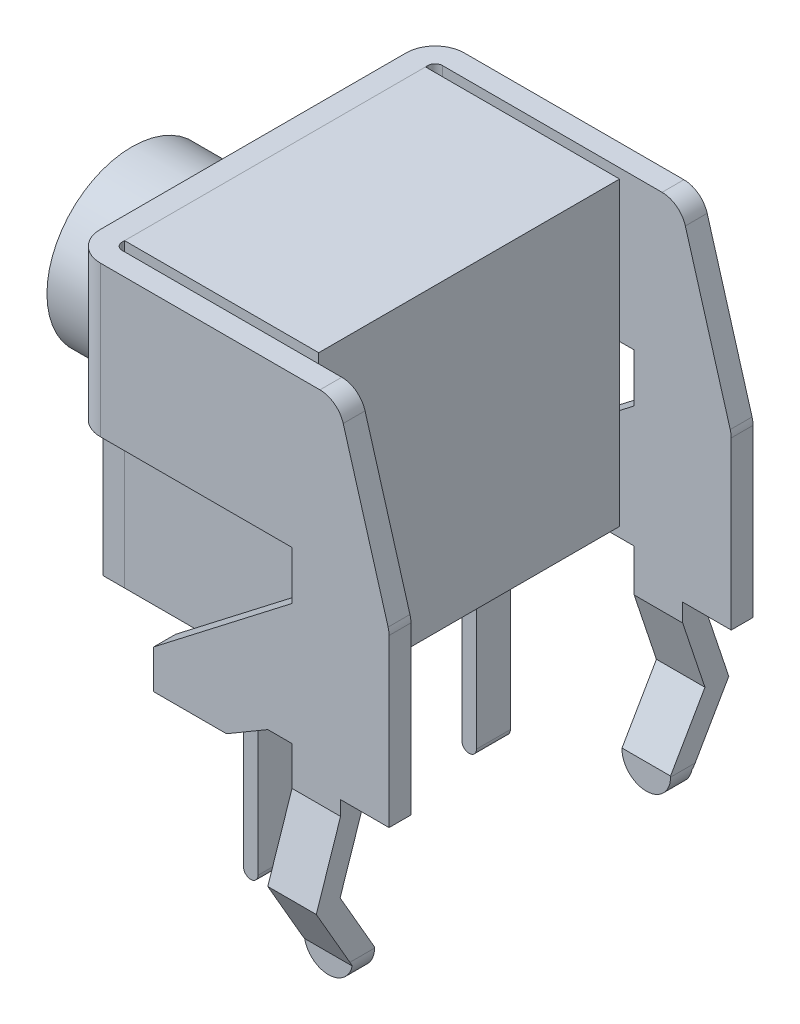
SolidWorks part; units mm, degrees
ref_plane "Front" through (0, 0, 0) normal (0, 0, 1) x (1, 0, 0)
ref_plane "Top" through (0, 0, 0) normal (0, 1, 0) x (1, 0, 0)
ref_plane "Right" through (0, 0, 0) normal (1, 0, 0) x (0, 0, -1)
sketch "草图1" plane through (0, 0, 0) normal (0, 0, 1) x (1, 0, 0)
  line L0 (0, 3.1) -> (0, -3.1)
  line L1 (0, -4) -> (2.4, -4)
  line L2 (6.55, -4) -> (6.55, -0.5)
  line L3 (6.55, -0.5) -> (5.5, 3.1)
  line L4 (5.5, 3.1) -> (0, 3.1)
  line L5 (0, -3.1) -> (0, -4)
  line L6 (2.4, -4) -> (2.4, -7.35) construction
  line L7 (1.0542, -7.5) -> (4.3688, -7.5) construction
  line L8 (2.7, -7.35) -> (2.7, -4) construction
  line L9 (4.55, -4) -> (4.55, -7)
  line L10 (2.7, -4) -> (4.55, -4)
  line L11 (5.55, -7) -> (5.55, -4)
  line L12 (5.55, -4) -> (6.55, -4)
  line L13 (2.4, -4) -> (2.7, -4)
  arc A0 (2.4, -7.35) -> (2.7, -7.35) centre (2.55, -7.35) ccw construction
  arc A1 (4.55, -7) -> (5.55, -7) centre (5.05, -7) ccw
  dimension "D1" = 6.2
  dimension "D2" = 4
  dimension "D3" = 0.3
  dimension "D4" = 1
  dimension "D5" = 2.5
  dimension "D6" = 2.55
  dimension "D7" = 4
  dimension "D8" = 3.5
  dimension "D9" = 5.5
  dimension "D10" = 0.5
extrude "凸台-拉伸1" add sketch "草图1" along normal blind 10 and the other way blind 10
sketch "草图2" plane through (0, 0, 0) normal (1, 0, 0) x (0, 0, -1)
  line L0 (3.75, 3.7782) -> (3.75, -4.3)
  line L1 (3.75, -4.3) -> (4.25, -5.8)
  line L2 (4.25, -5.8) -> (3.5, -7.1)
  line L3 (3.5, -7.1) -> (3.5, -7.9924)
  line L4 (10, 3.1) -> (-10, 3.1) construction
  dimension "D1" = 3.75
  dimension "D2" = 3.5
  dimension "D3" = 0.5
  dimension "D4" = 1.5
  dimension "D5" = 2.8
  dimension "D6" = 7.4
extrude "切除-拉伸1" cut sketch "草图2" against normal through all both and the other way through all
mirror "镜向1" about plane through (0, 0, 0) normal (0, 0, 1) of "切除-拉伸1"
fillet "圆角1" radius 0.6 2 edges at (0, -0.45, -3.75) (0, -0.45, 3.75)
fillet "圆角2" radius 0.5 2 edges at (5.5, 3.1, 0) (6.55, -0.5, 0)
shell "抽壳1" thickness 0.45 removed face at (1.6752, -4, 0) removed face at (4.55, -5.275, 0) removed face at (5.05, -7.1501, 0) removed face at (5.55, -5.275, 0) removed face at (6.05, -4, 0) removed face at (6.55, -2.2857, 0) removed face at (6.5425, -0.5011, 0) removed face at (6.0675, 1.1543, 0) removed face at (5.395, 2.96, 0) removed face at (1.8669, 3.1, 0)
sketch "草图4" plane through (0, 0, 3.75) normal (0, 0, 1) x (1, 0, 0)
  line L0 (-1.45, 0) -> (4.55, 0)
  line L1 (4.55, 0) -> (4.55, -1)
  line L2 (4.55, -1) -> (1.7, -3.2)
  line L3 (1.7, -3.2) -> (1.7, -4)
  line L4 (0.6, -4) -> (4.55, -4) construction
  line L5 (1.7, -4) -> (3.2, -4)
  line L6 (3.2, -4) -> (4.05, -3.5)
  line L7 (4.05, -3.5) -> (4.55, -3.5)
  line L8 (4.55, -3.5) -> (4.55, -9.5)
  line L9 (4.55, -9.5) -> (-1.45, -9.5)
  line L10 (-1.45, -9.5) -> (-1.45, 0)
  line L11 (2.7, -7.35) -> (2.7, -4) construction
  line L12 (2.7, -4) -> (4.55, -4) construction
  dimension "D1" = 0.8
  dimension "D2" = 1
  dimension "D3" = 0.5
  dimension "D4" = 0.5
  dimension "D5" = 0.5
  dimension "D6" = 1.5
  dimension "D7" = 6
  dimension "D8" = 6
extrude "切除-拉伸2" cut sketch "草图4" against normal blind 0.65
mirror "镜向2" about plane through (0, 0, 0) normal (0, 0, 1) of "切除-拉伸2"
sketch "草图5" plane through (0, 0, 0) normal (-1, 0, 0) x (0, 0, 1)
  line L0 (0, -0.5) -> (0, 3.1) construction
  line L1 (-3.1, 3.1) -> (3.1, 3.1) construction
  line L2 (-3.1, 3.1) -> (-3.1, -3.1) construction
  line L3 (-3.1, -3.1) -> (3.1, -3.1) construction
  line L4 (3.1, 3.1) -> (3.1, -3.1) construction
  line L5 (0, -3.1) -> (0, 3.1) construction
  line L6 (-3.1, 0) -> (3.1, 0) construction
  line L7 (-3.15, 3.1) -> (3.15, 3.1) construction
  line L8 (0, 0) -> (-2.1213, 2.1213) construction
  line L9 (-5, -3.1) -> (5, -3.1)
  line L10 (-5, -3.1) -> (-5, -5.1)
  line L11 (-5, -5.1) -> (5, -5.1)
  line L12 (5, -3.1) -> (5, -5.1)
  line L13 (0, -5.1) -> (0, -3.1) construction
  line L14 (-5, -4.1) -> (5, -4.1) construction
  circle A0 centre (0, 0) radius 3 construction
  circle A1 centre (-2.1213, 2.1213) radius 0.5
  circle A2 centre (2.1213, 2.1213) radius 0.5
  circle A3 centre (2.1213, -2.1213) radius 0.5
  circle A4 centre (-2.1213, -2.1213) radius 0.5
  circle A5 centre (0, 0) radius 1.75
  point P25 (0, 0)
  point P210 (0, -4.1)
  point P304 (0, 0)
  dimension "D3" = 6
  dimension "D4" = 1
  dimension "D7" = 3.5
  dimension "D1" = 2
  dimension "D2" = 10
  dimension "D5" = 45
  dimension "D6" = 4
extrude "切除-拉伸3" cut sketch "草图5" against normal up to surface (0.45 mm away) up to face at (0.45, -0.225, 0)
sketch "草图6" plane through (0.45, 0, 0) normal (1, 0, 0) x (0, 0, -1)
  line L0 (-3.1, 3.1) -> (-3.1, -3.1) construction
  line L1 (3.1, 3.1) -> (-3.1, 3.1) construction
  line L2 (3.1, 3.1) -> (3.1, -3.1) construction
  line L3 (-3.1, 3.1) -> (-3.1, -3.1)
  line L4 (3.1, 3.1) -> (-3.1, 3.1)
  line L5 (3.1, 3.1) -> (3.1, -3.1)
  line L6 (3.1, -3.1) -> (-3.1, -3.1) construction
  line L7 (3.1, -3.1) -> (-3.1, -3.1)
extrude "凸台-拉伸2" add sketch "草图6" along normal blind 4 separate body
sketch "草图7" plane through (0, 0, 0) normal (1, 0, 0) x (0, 0, -1)
  line L0 (2.25, -2.8) -> (2.25, -7.8)
  dimension "D1" = 2.25
  dimension "D2" = 2.8
  dimension "D3" = 5
extrude "拉伸-薄壁1" add sketch "草图7" along normal blind 4 separate body thin thin type mid plane wall 0.7
sketch "草图8" plane through (0, 0, 0) normal (0, 0, 1) x (1, 0, 0)
  line L0 (2.7, -7.35) -> (2.7, -4) construction
  line L1 (2.4, -4) -> (2.4, -7.35) construction
  line L2 (2.7, -7.35) -> (2.7, -1.7554)
  line L3 (2.4, -1.7554) -> (2.4, -7.35)
  line L4 (2.4, -1.7554) -> (2.7, -1.7554)
  arc A0 (2.4, -7.35) -> (2.7, -7.35) centre (2.55, -7.35) ccw construction
  arc A1 (2.4, -7.35) -> (2.7, -7.35) centre (2.55, -7.35) ccw
extrude "切除-拉伸4" cut sketch "草图8" against normal blind 4 flip side to cut
mirror "镜向3" about plane through (0, 0, 0) normal (0, 0, 1) of bodies 109
combine bodies "组合1" operation type add bodies to combine 109 110 107
sketch "草图9" plane through (0.45, 0, 0) normal (-1, 0, 0) x (0, 0, 1)
  circle A1 centre (-2.1213, 2.1213) radius 0.5
  circle A2 centre (-2.1213, 2.1213) radius 0.5
  circle A3 centre (0, 0) radius 1.75
  circle A4 centre (0, 0) radius 1.75
  circle A5 centre (-2.1213, -2.1213) radius 0.5
  circle A6 centre (-2.1213, -2.1213) radius 0.5
  circle A7 centre (2.1213, -2.1213) radius 0.5
  circle A8 centre (2.1213, -2.1213) radius 0.5
  circle A9 centre (2.1213, 2.1213) radius 0.5
  circle A10 centre (2.1213, 2.1213) radius 0.5
  dimension "D1" = 0
  dimension "D3" = 0
  dimension "D4" = 0
  dimension "D5" = 0
  dimension "D6" = 0
extrude "凸台-拉伸3" add sketch "草图9" along normal offset from surface (0.75 mm away) 0.3 contours A2 | A10 | A8 | A6 region at (0.45, 2.1213, -2.1213) up to face at (0, -2.6213, -2.1213) offset beyond the face yes
extrude "凸台-拉伸4" add sketch "草图9<4>" along normal offset from surface (2.95 mm away) 2.5 contours A4 region at (0.45, 0, 0) up to face at (0, -2.6213, -2.1213) offset beyond the face yes
sketch "草图9<4>" plane through (0.45, 0, 0) normal (-1, 0, 0) x (0, 0, 1) same geometry as "草图9"
sketch "草图10" plane through (0, -4, 0) normal (0, -1, 0) x (1, 0, 0)
  line L0 (2.55, 2.25) -> (2.55, 1.9) construction
  line L1 (2.4, 1.9) -> (2.7, 1.9) construction
  line L4 (5.55, 4.25) -> (4.55, 4.25) construction
  circle A0 centre (5.05, 3.5) radius 1
  circle A1 centre (2.55, 2.25) radius 0.5
  point P13 (5.05, 4.25)
  dimension "D1" = 1
  dimension "D2" = 2
  dimension "D3" = 2.25
  dimension "D4" = 3.5
